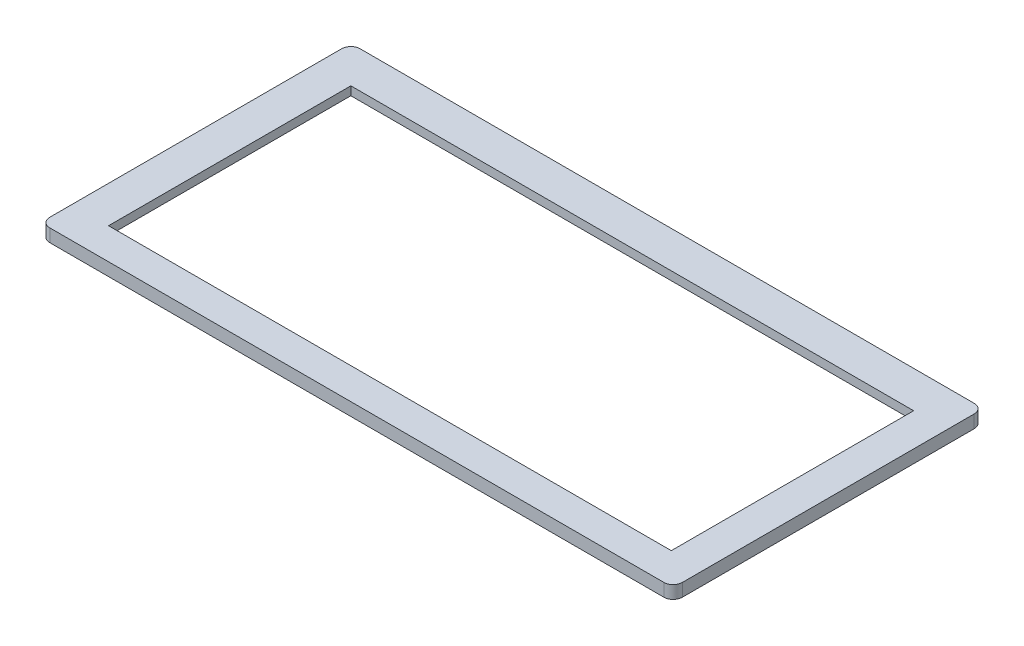
SolidWorks part; units mm, degrees
ref_plane "Front Plane" through (0, 0, 0) normal (0, 0, 1) x (1, 0, 0)
ref_plane "Top Plane" through (0, 0, 0) normal (0, 1, 0) x (1, 0, 0)
ref_plane "Right Plane" through (0, 0, 0) normal (1, 0, 0) x (0, 0, -1)
sketch "Sketch1" plane through (0, 0, 0) normal (0, 1, 0) x (1, 0, 0)
  line L0 (-142.8618, 0) -> (191.3602, 0) construction
  line L1 (0, 90.7825) -> (0, -132.7671) construction
  line L2 (-160.275, 78.7825) -> (160.275, 78.7825)
  line L3 (160.275, 78.7825) -> (160.275, -66.2175)
  line L4 (160.275, -66.2175) -> (-160.275, -66.2175)
  line L5 (-160.275, -66.2175) -> (-160.275, 78.7825)
  line L6 (-172.275, 90.7825) -> (172.275, 90.7825)
  line L7 (172.275, 90.7825) -> (172.275, -78.2175)
  line L8 (172.275, -78.2175) -> (-172.275, -78.2175)
  line L9 (-172.275, -78.2175) -> (-172.275, 90.7825)
  dimension "D1" = 320.55
  dimension "D2" = 145
  dimension "D3" = 12
  dimension "D4" = 12
  dimension "D5" = 12
  dimension "D6" = 12
extrude "Boss-Extrude1" add sketch "Sketch1" along normal blind 7
sketch "Sketch3" plane through (0, 0, 0) normal (0, -1, 0) x (1, 0, 0)
  line L0 (-22.72, -82.0825) -> (-47.57, -82.0825)
  line L1 (-22.72, -86.5825) -> (-22.72, -82.0825)
  line L2 (-78.72, -86.5825) -> (-22.72, -86.5825)
  line L3 (-78.72, -82.0825) -> (-78.72, -86.5825)
  line L4 (-53.87, -82.0825) -> (-78.72, -82.0825)
  line L5 (-53.87, -78.7825) -> (-53.87, -82.0825)
  line L6 (-47.57, -78.7825) -> (-53.87, -78.7825)
  line L7 (-47.57, -82.0825) -> (-47.57, -78.7825)
  line L16 (160.275, -78.7825) -> (-160.275, -78.7825) construction
  line L17 (-130.175, 66.2175) -> (-123.875, 66.2175)
  line L18 (146.225, -82.0825) -> (121.375, -82.0825)
  line L19 (146.225, -86.5825) -> (146.225, -82.0825)
  line L20 (90.225, -86.5825) -> (146.225, -86.5825)
  line L21 (90.225, -82.0825) -> (90.225, -86.5825)
  line L22 (115.075, -82.0825) -> (90.225, -82.0825)
  line L23 (115.075, -78.7825) -> (115.075, -82.0825)
  line L24 (121.375, -78.7825) -> (115.075, -78.7825)
  line L25 (121.375, -82.0825) -> (121.375, -78.7825)
  line L26 (71.33, -86.5825) -> (71.33, -82.0825)
  line L27 (15.33, -86.5825) -> (71.33, -86.5825)
  line L28 (15.33, -82.0825) -> (15.33, -86.5825)
  line L29 (40.18, -82.0825) -> (15.33, -82.0825)
  line L30 (40.18, -78.7825) -> (40.18, -82.0825)
  line L31 (46.48, -78.7825) -> (40.18, -78.7825)
  line L32 (46.48, -82.0825) -> (46.48, -78.7825)
  line L33 (71.33, -82.0825) -> (46.48, -82.0825)
  line L34 (-160.275, -78.7825) -> (-160.275, -50.3825) construction
  line L43 (-160.275, -44.0825) -> (-160.275, -50.3825)
  line L44 (-160.275, -44.0825) -> (-163.575, -44.0825)
  line L53 (163.575, 11.9175) -> (163.575, 32.2175)
  line L54 (-160.275, 66.2175) -> (160.275, 66.2175) construction
  line L55 (160.275, 66.2175) -> (160.275, -78.7825) construction
  line L56 (151.2867, -7.345) -> (183.3703, -7.345) construction
  line L57 (0, 81.7249) -> (0, 49.7201) construction
  line L58 (160.275, -40.5825) -> (163.575, -40.5825)
  line L59 (163.575, -40.5825) -> (163.575, -15.7325)
  line L60 (163.575, -15.7325) -> (168.075, -15.7325)
  line L61 (168.075, -15.7325) -> (168.075, -71.7325)
  line L62 (168.075, -71.7325) -> (163.575, -71.7325)
  line L63 (163.575, -71.7325) -> (163.575, -46.8825)
  line L64 (160.275, -46.8825) -> (163.575, -46.8825)
  line L65 (160.275, -40.5825) -> (160.275, -46.8825)
  line L66 (160.275, 32.2175) -> (163.575, 32.2175)
  line L68 (163.575, 58.8175) -> (168.075, 58.8175)
  line L69 (168.075, 58.8175) -> (168.075, 11.9175)
  line L70 (168.075, 11.9175) -> (163.575, 11.9175)
  line L72 (160.275, 38.5175) -> (163.575, 38.5175)
  line L73 (160.275, 32.2175) -> (160.275, 38.5175)
  line L74 (146.225, 74.0175) -> (146.225, 69.5175)
  line L75 (90.225, 74.0175) -> (146.225, 74.0175)
  line L76 (90.225, 69.5175) -> (90.225, 74.0175)
  line L77 (115.075, 69.5175) -> (90.225, 69.5175)
  line L78 (115.075, 66.2175) -> (115.075, 69.5175)
  line L79 (121.375, 66.2175) -> (115.075, 66.2175)
  line L80 (121.375, 69.5175) -> (121.375, 66.2175)
  line L81 (146.225, 69.5175) -> (121.375, 69.5175)
  line L82 (15.33, 74.0175) -> (71.33, 74.0175)
  line L83 (15.33, 69.5175) -> (15.33, 74.0175)
  line L84 (40.18, 69.5175) -> (15.33, 69.5175)
  line L85 (40.18, 66.2175) -> (40.18, 69.5175)
  line L86 (46.48, 66.2175) -> (40.18, 66.2175)
  line L87 (46.48, 69.5175) -> (46.48, 66.2175)
  line L88 (71.33, 69.5175) -> (46.48, 69.5175)
  line L89 (71.33, 74.0175) -> (71.33, 69.5175)
  line L106 (0, -99.7125) -> (0, -58.961) construction
  line L115 (163.575, 38.5175) -> (163.575, 58.8175)
  line L116 (-160.275, 66.2175) -> (160.275, 66.2175) construction
  line L117 (-160.275, -50.3825) -> (-163.575, -50.3825)
  line L118 (-163.575, -44.0825) -> (-163.575, -19.2325)
  line L119 (-163.575, -50.3825) -> (-163.575, -75.2325)
  line L120 (-163.575, -19.2325) -> (-168.075, -19.2325)
  line L121 (-168.075, -19.2325) -> (-168.075, -75.2325)
  line L122 (-168.075, -75.2325) -> (-163.575, -75.2325)
  line L123 (-160.275, -78.7825) -> (-160.275, 66.2175) construction
  line L124 (-160.275, 38.5175) -> (-160.275, 32.2175)
  line L125 (-160.275, 38.5175) -> (-163.575, 38.5175)
  line L126 (-160.275, 32.2175) -> (-163.575, 32.2175)
  line L127 (-163.575, 38.5175) -> (-163.575, 58.8175)
  line L128 (-163.575, 58.8175) -> (-168.075, 58.8175)
  line L129 (-168.075, 58.8175) -> (-168.075, 11.9175)
  line L130 (-168.075, 11.9175) -> (-163.575, 11.9175)
  line L131 (-163.575, 11.9175) -> (-163.575, 32.2175)
  line L132 (-160.275, 66.2175) -> (-160.275, 38.5175) construction
  line L133 (-123.875, 66.2175) -> (-123.875, 69.5175)
  line L134 (-123.875, 69.5175) -> (-99.025, 69.5175)
  line L135 (-99.025, 69.5175) -> (-99.025, 74.0175)
  line L136 (-99.025, 74.0175) -> (-155.025, 74.0175)
  line L137 (-155.025, 74.0175) -> (-155.025, 69.5175)
  line L138 (-155.025, 69.5175) -> (-130.175, 69.5175)
  line L139 (-130.175, 69.5175) -> (-130.175, 66.2175)
  line L140 (-160.275, 66.2175) -> (-130.175, 66.2175) construction
  line L141 (-55.375, 66.2175) -> (-49.075, 66.2175)
  line L142 (-49.075, 66.2175) -> (-49.075, 69.5175)
  line L143 (-49.075, 69.5175) -> (-24.225, 69.5175)
  line L144 (-24.225, 69.5175) -> (-24.225, 74.0175)
  line L145 (-24.225, 74.0175) -> (-80.225, 74.0175)
  line L146 (-80.225, 74.0175) -> (-80.225, 69.5175)
  line L147 (-80.225, 69.5175) -> (-55.375, 69.5175)
  line L148 (-55.375, 69.5175) -> (-55.375, 66.2175)
  line L149 (-123.875, 66.2175) -> (-55.375, 66.2175) construction
  line L150 (-47.57, -78.7825) -> (0, -78.7825) construction
  line L151 (160.275, -78.7825) -> (-160.275, -78.7825) construction
  line L152 (0, -78.7825) -> (40.18, -78.7825) construction
  dimension "D5" = 6.3
  dimension "D6" = 4.5
  dimension "D7" = 56
  dimension "D8" = 6.3
  dimension "D9" = 6.3
  dimension "D10" = 3.3
  dimension "D11" = 56
  dimension "D12" = 47.57
  dimension "D13" = 6.3
  dimension "D14" = 4.5
  dimension "D15" = 56
  dimension "D16" = 6.3
  dimension "D17" = 6.3
  dimension "D18" = 4.5
  dimension "D19" = 56
  dimension "D20" = 3.3
  dimension "D21" = 28.4
  dimension "D22" = 20.3
  dimension "D23" = 4.5
  dimension "D24" = 3.3
  dimension "D25" = 27.7
  dimension "D26" = 3.3
  dimension "D27" = 4.5
  dimension "D28" = 56
  dimension "D29" = 30.1
  dimension "D30" = 40.18
  dimension "D31" = 180
  dimension "56" = 56
  dimension "D32" = 6.3
  dimension "D33" = 38.9
  dimension "D34" = 6.3
  dimension "D35" = 27.7
  dimension "D36" = 31.9
  dimension "D37" = 56
  dimension "D38" = 38.9
  dimension "D39" = 6.3
  dimension "D40" = 3.3
  dimension "D41" = 4.5
  dimension "D42" = 40.18
  dimension "D43" = 6.3
  dimension "D44" = 3.3
  dimension "D45" = 46.9
  dimension "D46" = 6.3
  dimension "D47" = 3.3
  dimension "D48" = 4.5
  dimension "D49" = 3.3
  dimension "D50" = 4.5
  dimension "D51" = 3.3
  dimension "D52" = 4.5
  dimension "D53" = 56
  dimension "D54" = 4.5
  dimension "D55" = 3.3
  dimension "D56" = 4.5
  dimension "D57" = 3.3
  dimension "D58" = 56
  dimension "D59" = 68.5
  dimension "D60" = 180
fillet "Fillet1" radius 5 1 edges at (172.275, 3.5, 78.2175)
fillet "Fillet2" radius 5 1 edges at (-172.275, 3.5, -90.7825)
fillet "Fillet3" radius 5 1 edges at (-172.275, 3.5, 78.2175)
extrude "Cut-Extrude2" cut sketch "Sketch3" against normal blind 2.3
fillet "Fillet5" radius 5 1 edges at (172.275, 3.5, -90.7825)
sketch "Sketch4" plane through (0, 0, 0) normal (0, -1, 0) x (1, 0, 0)
  circle A8 centre (-165.5428, 71.4853) radius 1.325
  circle A9 centre (-89.625, 71.7675) radius 1.325
  circle A10 centre (80.7775, 71.7675) radius 1.325
  circle A11 centre (165.5328, 71.4853) radius 1.325
  circle A12 centre (165.5328, -84.0502) radius 1.325
  circle A13 centre (80.7775, -84.3325) radius 1.325
  circle A14 centre (-89.625, -84.0502) radius 1.325
  circle A15 centre (-165.5428, -84.0502) radius 1.325
  point P6 (-165.5428, 71.4853)
  point P7 (-89.625, 71.7675)
  point P9 (80.7775, 71.7675)
  point P11 (80.7775, -84.3325)
  point P12 (-89.625, -84.0502)
  point P13 (-165.5428, -84.0502)
  point P16 (165.5328, 71.4853)
  point P22 (165.5328, -84.0502)
extrude "Cut-Extrude3" cut sketch "Sketch4" against normal blind 4
fillet "Fillet6" radius 3 66 edges at (-78.72, 1.15, -86.5825) (-78.72, 1.15, -82.0825) (-22.72, 1.15, -86.5825) (-22.72, 1.15, -82.0825) (-53.87, 1.15, -82.0825) (-47.57, 1.15, -82.0825) (15.33, 1.15, -86.5825) (15.33, 1.15, -82.0825) (71.33, 1.15, -86.5825) (71.33, 1.15, -82.0825) (40.18, 1.15, -82.0825) (46.48, 1.15, -82.0825) (90.225, 1.15, -86.5825) (90.225, 1.15, -82.0825) (146.225, 1.15, -86.5825) (146.225, 1.15, -82.0825) (115.075, 1.15, -82.0825) (121.375, 1.15, -82.0825) (163.575, 1.15, -71.7325) (168.075, 1.15, -71.7325) (168.075, 1.15, -15.7325) (163.575, 1.15, -15.7325) (163.575, 1.15, -46.8825) (163.575, 1.15, -40.5825) (163.575, 1.15, 11.9175) (168.075, 1.15, 11.9175) (163.575, 1.15, 58.8175) (168.075, 1.15, 58.8175) (163.575, 1.15, 32.2175) (163.575, 1.15, 38.5175) (146.225, 1.15, 69.5175) (146.225, 1.15, 74.0175) (90.225, 1.15, 74.0175) (90.225, 1.15, 69.5175) (115.075, 1.15, 69.5175) (121.375, 1.15, 69.5175) (71.33, 1.15, 69.5175) (71.33, 1.15, 74.0175) (15.33, 1.15, 69.5175) (15.33, 1.15, 74.0175) (46.48, 1.15, 69.5175) (40.18, 1.15, 69.5175) (-24.225, 1.15, 69.5175) (-24.225, 1.15, 74.0175) (-80.225, 1.15, 74.0175) (-80.225, 1.15, 69.5175) (-49.075, 1.15, 69.5175) (-55.375, 1.15, 69.5175) (-155.025, 1.15, 69.5175) (-155.025, 1.15, 74.0175) (-99.025, 1.15, 69.5175) (-99.025, 1.15, 74.0175) (-123.875, 1.15, 69.5175) (-130.175, 1.15, 69.5175) (-163.575, 1.15, 11.9175) (-168.075, 1.15, 11.9175) (-168.075, 1.15, 58.8175) (-163.575, 1.15, 58.8175) (-163.575, 1.15, 38.5175) (-163.575, 1.15, 32.2175) (-163.575, 1.15, -19.2325) (-168.075, 1.15, -19.2325) (-168.075, 1.15, -75.2325) (-163.575, 1.15, -75.2325) (-163.575, 1.15, -50.3825) (-163.575, 1.15, -44.0825)
sketch "Sketch5" plane through (0, 7, 0) normal (0, 1, 0) x (1, 0, 0)
  line L0 (-160.275, 78.7825) -> (-160.275, -66.2175)
  line L1 (-160.275, -66.2175) -> (160.275, -66.2175)
  line L2 (160.275, -66.2175) -> (160.275, 78.7825)
  line L3 (160.275, 78.7825) -> (-160.275, 78.7825)
  line L4 (-152.275, 70.7825) -> (-152.275, -61.2175)
  line L5 (-152.275, -61.2175) -> (154.275, -61.2175)
  line L6 (154.275, -61.2175) -> (154.275, 70.7825)
  line L7 (154.275, 70.7825) -> (-152.275, 70.7825)
  point P13 (-136.1702, 67.956)
  dimension "D1" = 8
  dimension "D2" = 5
  dimension "D3" = 8
  dimension "D4" = 6
extrude "Boss-Extrude2" add sketch "Sketch5" against normal blind 4.7
